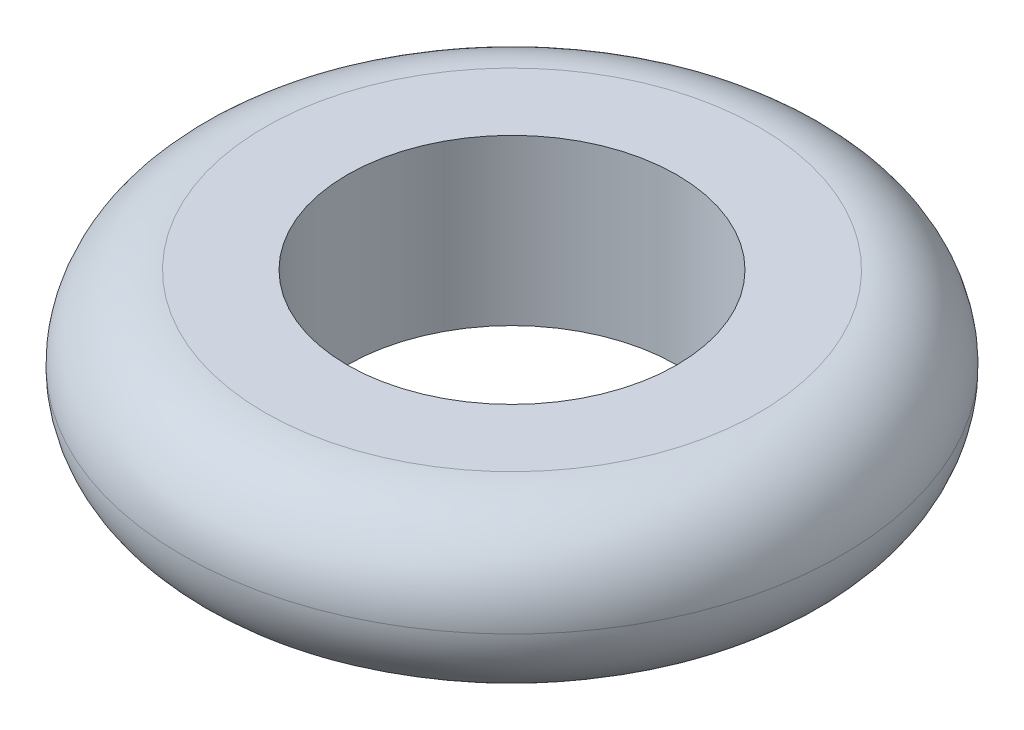
SolidWorks part; units mm, degrees
material "Rubber"
ref_plane "Front Plane" through (0, 0, 0) normal (0, 0, 1) x (1, 0, 0)
ref_plane "Top Plane" through (0, 0, 0) normal (0, 1, 0) x (1, 0, 0)
ref_plane "Right Plane" through (0, 0, 0) normal (1, 0, 0) x (0, 0, -1)
sketch "Sketch1" plane through (0, 0, 0) normal (0, 1, 0) x (1, 0, 0)
  circle A0 centre (-1.0054, 0.377) radius 1
  circle A1 centre (-1.0054, 0.377) radius 2
  dimension "D1" = 2
extrude "Boss-Extrude1" add sketch "Sketch1" along normal blind 1
fillet "Fillet1" radius 0.5 2 edges at (-1.0054, 0, 1.623) (-1.0054, 1, 1.623)
